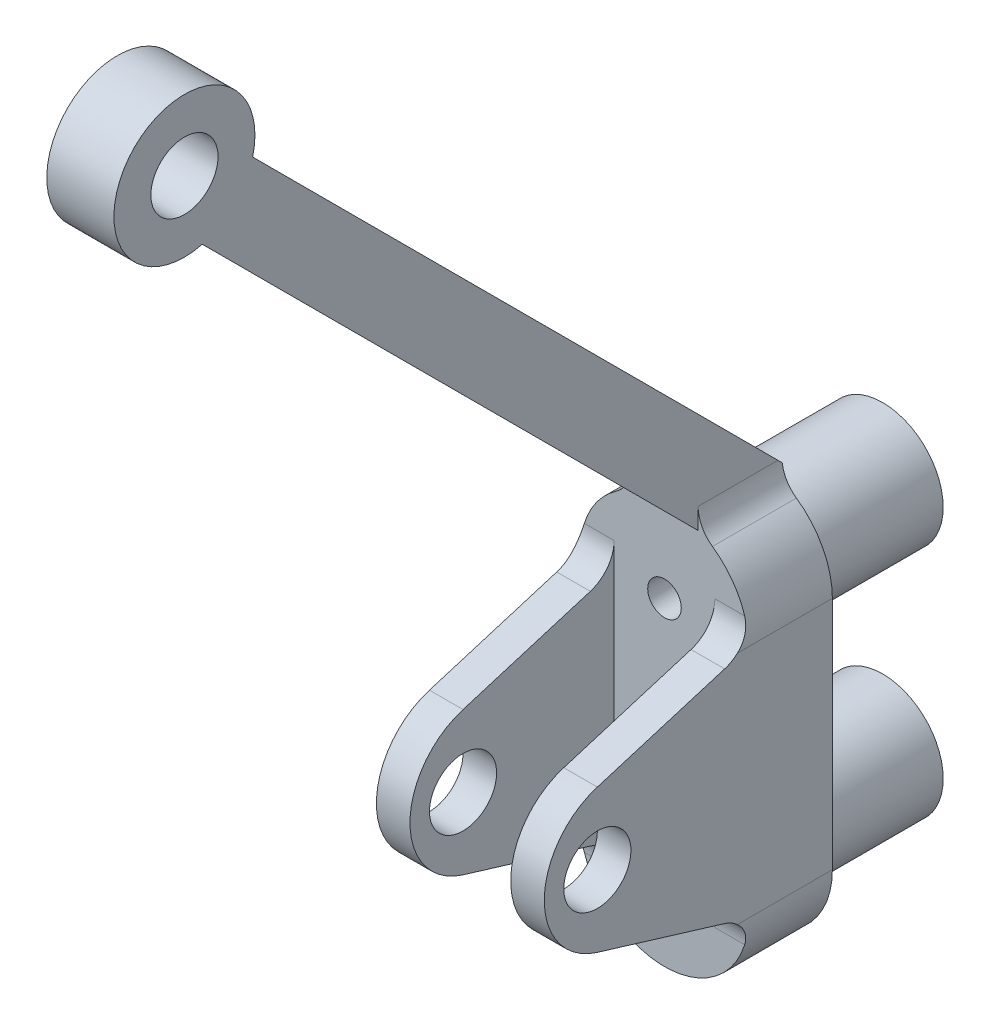
SolidWorks part; units mm, degrees
ref_plane "Front Plane" through (0, 0, 0) normal (0, 0, 1) x (1, 0, 0)
ref_plane "Top Plane" through (0, 0, 0) normal (0, 1, 0) x (1, 0, 0)
ref_plane "Right Plane" through (0, 0, 0) normal (1, 0, 0) x (0, 0, -1)
sketch "Sketch1" plane through (0, 0, 0) normal (0, 0, 1) x (1, 0, 0)
  line L0 (0, -3.5) -> (0, 3.5) construction
  line L1 (-2.5, -3.5) -> (-2.5, 3.5)
  line L2 (2.5, -3.5) -> (2.5, 3.5)
  arc A0 (-2.5, -3.5) -> (2.5, -3.5) centre (0, -3.5) ccw
  arc A1 (2.5, 3.5) -> (-2.5, 3.5) centre (0, 3.5) ccw
  circle A2 centre (0, 3.5) radius 0.5
  circle A3 centre (0, -3.5) radius 0.5
  point P2 (0, 0)
  dimension "D1" = 2.5
  dimension "D2" = 7
  dimension "D3" = 1
  dimension "D4" = 1
extrude "Boss-Extrude1" add sketch "Sketch1" along normal blind 2.5
sketch "Sketch2" plane through (2.5, 0, 0) normal (1, 0, 0) x (0, 0, -1)
  line L0 (-7, 2.1321) -> (-2.5, 3.5)
  line L1 (-2.5, -3.5) -> (-2.5, 3.5) construction
  line L2 (-2.5, 3.5) -> (-2.5, -3.5)
  line L3 (-2.5, -3.5) -> (-7, -2.1321)
  line L4 (0, 0) -> (-7, 0) construction
  circle A0 centre (-7, 0) radius 1
  arc A1 (-7, 2.1321) -> (-7, -2.1321) centre (-6.3519, 0) ccw
  dimension "D1" = 2
  dimension "D3" = 7
extrude "Boss-Extrude2" add sketch "Sketch2" against normal blind 1
mirror "Mirror1" about plane through (0, 0, 0) normal (1, 0, 0) of "Boss-Extrude2"
fillet "Fillet1" radius 1 4 edges at (-2, -3.5, 2.5) (2, -3.5, 2.5) (-2, 3.5, 2.5) (2, 3.5, 2.5)
sketch "Sketch3" plane through (0, 0, 0) normal (1, 0, 0) x (0, 0, -1)
  line L0 (-17.7979, 22.5479) -> (-1.25, 6) construction
  line L1 (0, 6) -> (-2.5, 6) construction
  line L2 (-17.7979, 22.5479) -> (-7, 0) construction
  line L3 (-7, 0) -> (-1.25, 6) construction
  line L4 (-16.2979, 22.5479) -> (0, 6.25)
  line L5 (-17.7979, 21.0479) -> (-2.5, 5.75)
  line L6 (0, 3.5) -> (0, 6) construction
  line L7 (0, 5.75) -> (0, 6.25)
  line L8 (-2.5, 5.75) -> (0, 5.75)
  line L9 (-2.5, 6) -> (-2.5, 4.2412) construction
  line L11 (-16.2979, 22.5479) -> (-17.7979, 21.0479) construction
  arc A0 (-16.2979, 22.5479) -> (-17.7979, 21.0479) centre (-17.7979, 22.5479) ccw
  circle A1 centre (-17.7979, 22.5479) radius 1
  dimension "D1" = 2
  dimension "D2" = 3
  dimension "D3" = 25
extrude "Boss-Extrude4" add sketch "Sketch3" along normal blind 1 and the other way blind 1
fillet "Fillet2" radius 1 2 edges at (-1, 5.7913, 1.25) (1, 5.7913, 1.25)
sketch "Sketch4" plane through (1, 0, 0) normal (1, 0, 0) x (0, 0, -1)
  circle A0 centre (-17.7979, 22.5479) radius 1
  circle A1 centre (-17.7979, 22.5479) radius 2.1
  dimension "D1" = 4.2
extrude "Boss-Extrude5" add sketch "Sketch4" against normal blind 2
sketch "Sketch5" plane through (0, 0, 0) normal (0, 0, -1) x (-1, 0, 0)
  circle A0 centre (0, 3.5) radius 0.5
  circle A1 centre (0, 3.5) radius 1.8
  circle A2 centre (0, -3.5) radius 1.8
  circle A3 centre (0, -3.5) radius 0.5
  dimension "D1" = 3.6
  dimension "D2" = 3.6
extrude "Boss-Extrude6" add sketch "Sketch5" along normal blind 4
